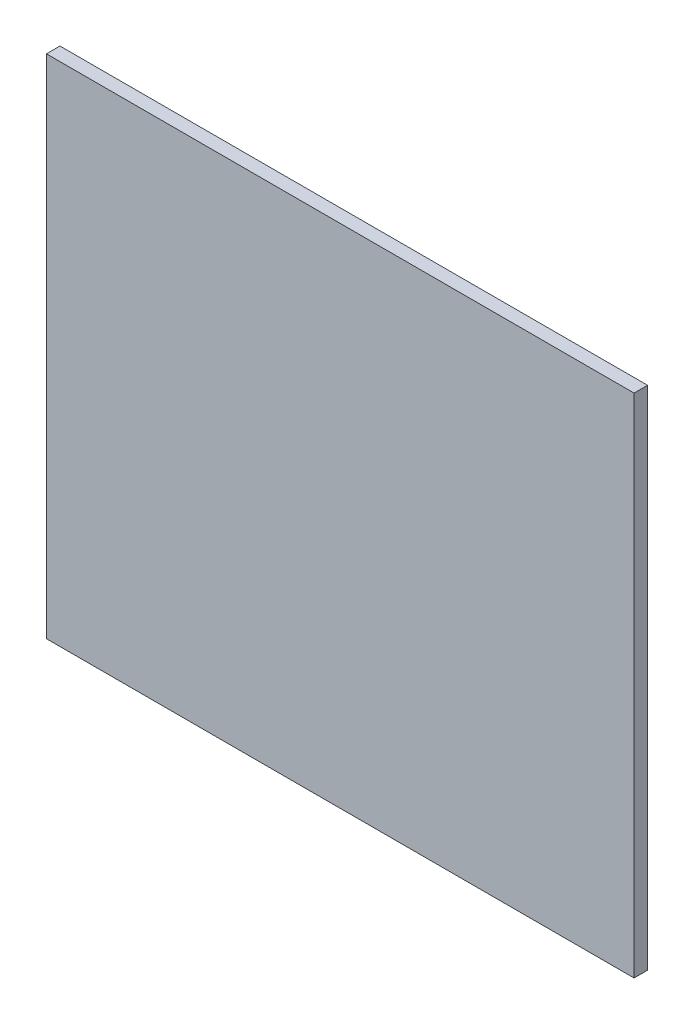
SolidWorks part; units mm, degrees
ref_plane "Plan de face" through (0, 0, 0) normal (0, 0, 1) x (1, 0, 0)
ref_plane "Plan de dessus" through (0, 0, 0) normal (0, 1, 0) x (1, 0, 0)
ref_plane "Plan de droite" through (0, 0, 0) normal (1, 0, 0) x (0, 0, -1)
sketch "Esquisse1" plane through (0, 0, 0) normal (0, 0, 1) x (1, 0, 0)
  line L1 (-33.1728, 31.2835) -> (53.8272, 31.2835)
  line L2 (-33.1728, 31.2835) -> (-33.1728, -43.7165)
  line L3 (-33.1728, -43.7165) -> (53.8272, -43.7165)
  line L4 (53.8272, 31.2835) -> (53.8272, -43.7165)
  dimension "D1" = 87
  dimension "D2" = 75
extrude "Boss.-Extru.1" add sketch "Esquisse1" along normal blind 2
sketch "Esquisse2" plane through (0, 0, 0) normal (0, 0, -1) x (-1, 0, 0)
  line L0 (33.1728, 31.2835) -> (33.1728, -43.7165) construction
  line L1 (33.1728, -2.9665) -> (28.1728, -2.9665)
  line L2 (33.1728, -2.9665) -> (33.1728, -9.4665)
  line L3 (33.1728, -9.4665) -> (28.1728, -9.4665)
  line L4 (28.1728, -2.9665) -> (28.1728, -9.4665)
  line L5 (33.1728, -2.9665) -> (33.1728, 31.2835) construction
  line L6 (-53.8272, 31.2835) -> (33.1728, 31.2835) construction
  line L7 (33.1728, -9.4665) -> (33.1728, -43.7165) construction
  dimension "D1" = 6.5
  dimension "D2" = 5
extrude "Boss.-Extru.2" add sketch "Esquisse2" along normal blind 5
sketch "Esquisse3" plane through (0, 0, -5) normal (0, 0, -1) x (-1, 0, 0)
  line L0 (33.1728, 31.2835) -> (33.1728, -2.9665) construction
  line L1 (33.1728, 3.7835) -> (23.1728, 3.7835)
  line L2 (33.1728, 3.7835) -> (33.1728, -16.2165)
  line L3 (33.1728, -16.2165) -> (23.1728, -16.2165)
  line L4 (23.1728, 3.7835) -> (23.1728, -16.2165)
  line L5 (28.1728, -16.2165) -> (28.1728, -43.7165) construction
  line L6 (33.1728, -43.7165) -> (-53.8272, -43.7165) construction
  dimension "D1" = 10
  dimension "D2" = 20
extrude "Boss.-Extru.3" add sketch "Esquisse3" along normal blind 10
